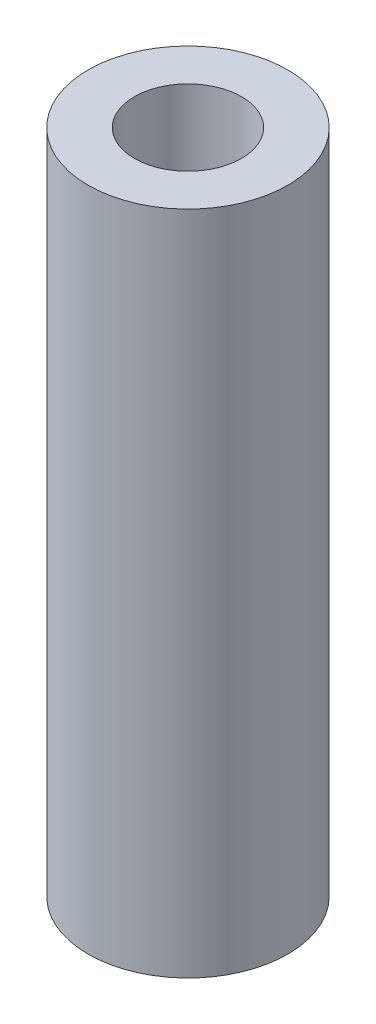
SolidWorks part; units mm, degrees
material "6061-T6 (SS)"
ref_plane "Front Plane" through (0, 0, 0) normal (0, 0, 1) x (1, 0, 0)
ref_plane "Top Plane" through (0, 0, 0) normal (0, 1, 0) x (1, 0, 0)
ref_plane "Right Plane" through (0, 0, 0) normal (1, 0, 0) x (0, 0, -1)
sketch "Sketch1" plane through (0, 0, 0) normal (0, 1, 0) x (1, 0, 0)
  circle A0 centre (0, 0) radius 2.5527
  circle A1 centre (0, 0) radius 4.7625
  dimension "D1" = 5.1054
  dimension "D2" = 9.525
extrude "Boss-Extrude1" add sketch "Sketch1" along normal mid plane 31.75
